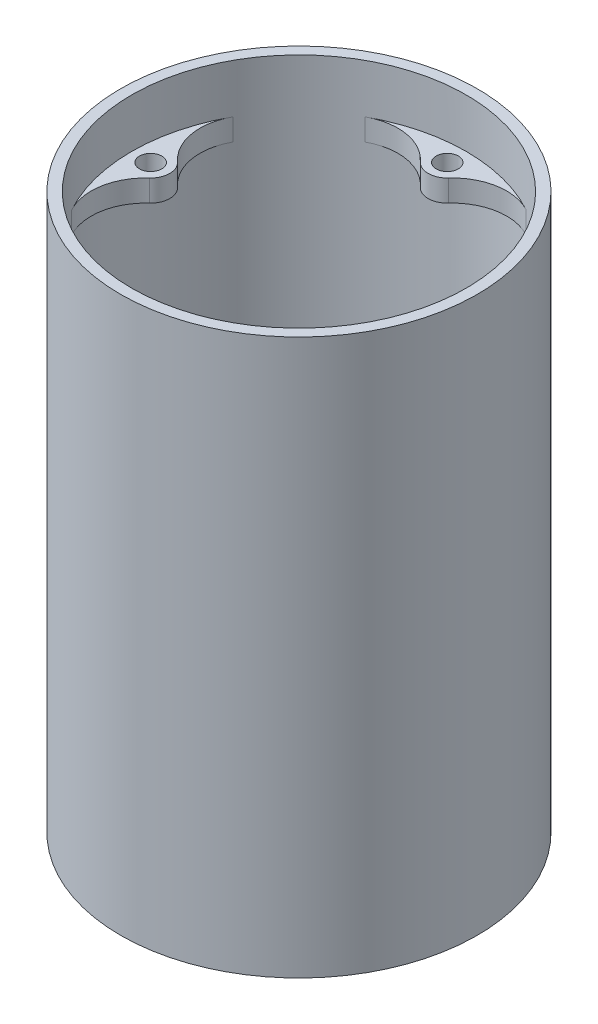
SolidWorks part; units mm, degrees
ref_plane "Front Plane" through (0, 0, 0) normal (0, 0, 1) x (1, 0, 0)
ref_plane "Top Plane" through (0, 0, 0) normal (0, 1, 0) x (1, 0, 0)
ref_plane "Right Plane" through (0, 0, 0) normal (1, 0, 0) x (0, 0, -1)
sketch "Sketch1" plane through (0, 0, 0) normal (0, 1, 0) x (1, 0, 0)
  circle A0 centre (0, 0) radius 30.75
  circle A1 centre (0, 0) radius 32.75
  dimension "D1" = 61.5
  dimension "D2" = 2
extrude "Boss-Extrude1" add sketch "Sketch1" along normal blind 102
ref_plane "Plane1" through (0, 93, 0) normal (0, 1, 0) x (1, 0, 0)
sketch "Sketch3" plane through (0, 93, 0) normal (0, 1, 0) x (1, 0, 0)
  line L0 (0, 30.75) -> (0, 27.25) construction
  line L1 (-3.5, 27.25) -> (-3.5, 30.8018)
  line L2 (3.5, 27.25) -> (3.5, 30.8018)
  line L3 (-3.5, 27.25) -> (3.5, 27.25) construction
  line L4 (27.25, -3.5) -> (30.8018, -3.5)
  line L5 (27.25, 3.5) -> (30.8018, 3.5)
  line L6 (-3.5, -27.25) -> (-3.5, -30.8018)
  line L7 (3.5, -27.25) -> (3.5, -30.8018)
  line L8 (-27.25, 3.5) -> (-30.8018, 3.5)
  line L9 (-27.25, -3.5) -> (-30.8018, -3.5)
  arc A0 (3.5, 30.8018) -> (-3.5, 30.8018) centre (0, 0) ccw
  arc A1 (-3.5, 27.25) -> (3.5, 27.25) centre (0, 27.25) ccw
  circle A2 centre (0, 0) radius 30.75 construction
  arc A3 (30.8018, -3.5) -> (30.8018, 3.5) centre (0, 0) ccw
  arc A4 (27.25, 3.5) -> (27.25, -3.5) centre (27.25, 0) ccw
  arc A5 (-3.5, -30.8018) -> (3.5, -30.8018) centre (0, 0) ccw
  arc A6 (3.5, -27.25) -> (-3.5, -27.25) centre (0, -27.25) ccw
  arc A7 (-30.8018, 3.5) -> (-30.8018, -3.5) centre (0, 0) ccw
  arc A8 (-27.25, -3.5) -> (-27.25, 3.5) centre (-27.25, 0) ccw
  circle A9 centre (0, 27.25) radius 2.05
  circle A10 centre (27.25, 0) radius 2.05
  circle A11 centre (0, -27.25) radius 2.05
  circle A12 centre (-27.25, 0) radius 2.05
  point P28 (0, 0)
  point P36 (0, 0)
  dimension "D1" = 7
  dimension "D3" = 62
  dimension "D5" = 4.1
  dimension "D2" = 3.5
  dimension "D4" = 4
  dimension "D6" = 4
extrude "Boss-Extrude2" add sketch "Sketch3" against normal blind 4
fillet "Fillet1" radius 10 8 edges at (30.5502, 91, 3.5) (30.5502, 91, -3.5) (-3.5, 91, 30.5502) (3.5, 91, 30.5502) (-30.5502, 91, -3.5) (-30.5502, 91, 3.5) (3.5, 91, -30.5502) (-3.5, 91, -30.5502)
